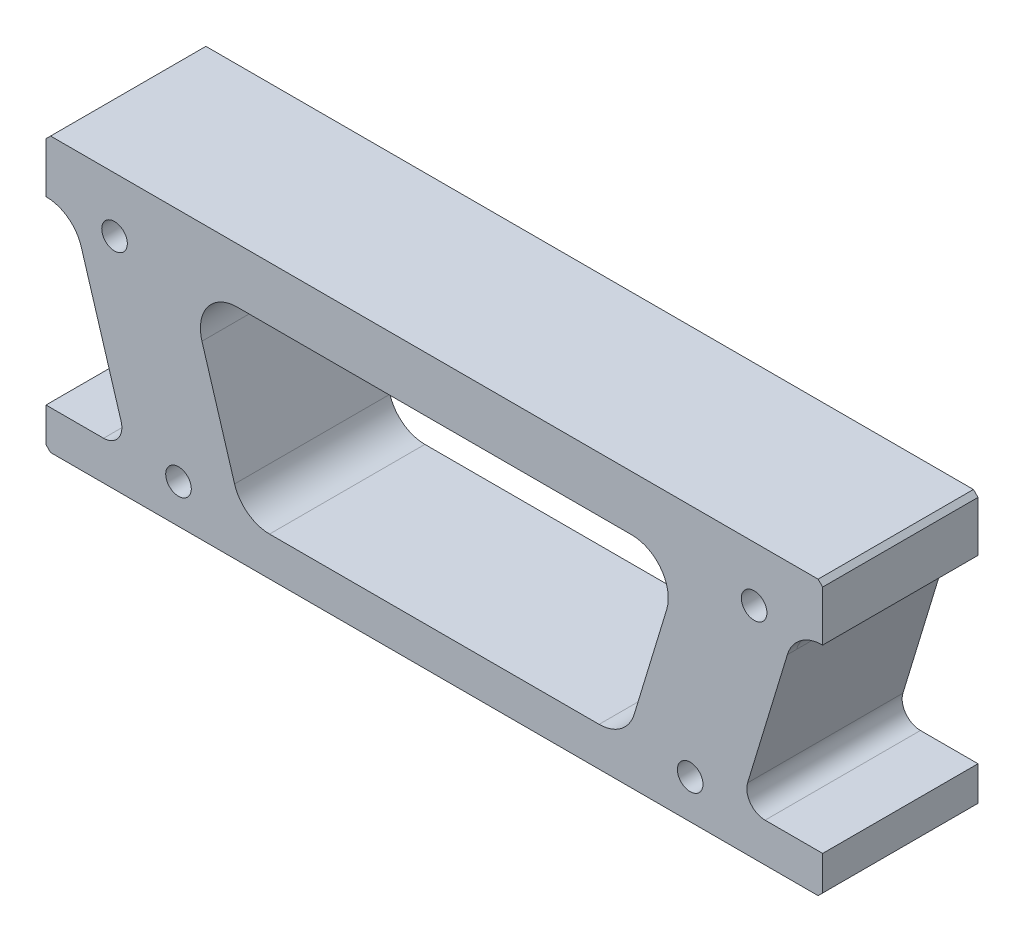
SolidWorks part; units mm, degrees
ref_plane "前视基准面" through (0, 0, 0) normal (0, 0, 1) x (1, 0, 0)
ref_plane "上视基准面" through (0, 0, 0) normal (0, 1, 0) x (1, 0, 0)
ref_plane "右视基准面" through (0, 0, 0) normal (1, 0, 0) x (0, 0, -1)
sketch "草图1" plane through (0, 0, 0) normal (0, 1, 0) x (1, 0, 0)
  line L1 (-42.5, 7.5) -> (42.5, 7.5)
  line L2 (-42.5, 7.5) -> (-42.5, -7.5)
  line L3 (-42.5, -7.5) -> (42.5, -7.5)
  line L4 (42.5, 7.5) -> (42.5, -7.5)
  line L5 (-42.5, 7.5) -> (42.5, -7.5) construction
  line L6 (-42.5, -7.5) -> (42.5, 7.5) construction
  dimension "D1" = 85
  dimension "D2" = 15
extrude "凸台-拉伸1" add sketch "草图1" along normal blind 30
sketch "草图2" plane through (0, 0, 7.5) normal (0, 0, 1) x (1, 0, 0)
  line L0 (0, 30) -> (0, 24) construction
  line L1 (0, 24) -> (-35, 24) construction
  line L2 (0, 24) -> (35, 24) construction
  line L3 (0, 24) -> (0, 4) construction
  line L4 (0, 4) -> (28, 4.2557) construction
  line L5 (0, 4) -> (-28, 4.2557) construction
  line L6 (0, 30) -> (0, 37.6117) construction
  line L7 (-42.5, 30) -> (42.5, 30) construction
  circle A0 centre (-35, 24) radius 1.4
  circle A1 centre (35, 24) radius 1.4
  circle A2 centre (28, 4.2557) radius 1.4
  circle A3 centre (-28, 4.2557) radius 1.4
extrude "切除-拉伸1" cut sketch "草图2" against normal blind 40
sketch "草图3" plane through (0, 0, 7.5) normal (0, 0, 1) x (1, 0, 0)
  line L0 (-27, 24) -> (27, 24)
  line L1 (-27, 24) -> (-21, 4.2557)
  line L2 (-21, 4.2557) -> (21, 4.2557)
  line L3 (0, 0) -> (0, 30) construction
  line L4 (-42.5, 30) -> (42.5, 30) construction
  line L5 (27, 24) -> (21, 4.2557)
  point P12 (0, 4.2557)
  point P13 (0, 24)
extrude "切除-拉伸2" cut sketch "草图3" against normal blind 40
fillet "圆角1" radius 4 4 edges at (-27, 24, 0) (27, 24, 0) (21, 4.2557, 0) (-21, 4.2557, 0)
sketch "草图5" plane through (0, 30, 0) normal (0, 1, 0) x (1, 0, 0)
  line L0 (-20, -4.5) -> (20, -4.5) construction
  line L1 (0, 4.5) -> (0, -4.5) construction
  line L2 (-35, 4.5) -> (0, 4.5) construction
  line L3 (0, 4.5) -> (35, 4.5) construction
  line L4 (0, 7.5) -> (0, 4.5) construction
  circle A0 centre (-35, 4.5) radius 1.8
  circle A1 centre (35, 4.5) radius 1.8
  circle A2 centre (-20, -4.5) radius 1.8
  circle A3 centre (20, -4.5) radius 1.8
  point P0 (0, 0)
extrude "切除-拉伸3" cut sketch "草图5" against normal blind 5
ref_plane "基准面1" through (0, 15, 0) normal (0, 1, 0) x (1, 0, 0)
chamfer "倒角1" distance 0.5 angle 45 4 edges at (-42.5, 0, 0) (42.5, 0, 0) (42.5, 30, 0) (-42.5, 30, 0)
sketch "草图6" plane through (0, 0, 7.5) normal (0, 0, 1) x (1, 0, 0)
  line L0 (-42.5, 24) -> (-39.5, 24)
  line L1 (-42.5, 29.5) -> (-42.5, 0.5) construction
  line L2 (-39.5, 24) -> (-33.5, 4.2557)
  line L3 (-33.5, 4.2557) -> (-42.5, 4.2557)
  line L4 (-25.431, 18.837) -> (-21.8621, 7.0927) construction
  line L5 (-25.431, 18.837) -> (-21.8621, 7.0927) construction
  line L6 (0, 30) -> (0, 0) construction
  line L7 (-42, 30) -> (42, 30) construction
  line L8 (-42.5, 24) -> (-42.5, 4.2557)
  line L9 (42.5, 24) -> (42.5, 4.2557)
  line L10 (33.5, 4.2557) -> (42.5, 4.2557)
  line L11 (39.5, 24) -> (33.5, 4.2557)
  line L12 (42.5, 24) -> (39.5, 24)
extrude "切除-拉伸4" cut sketch "草图6" against normal blind 24
fillet "圆角3" radius 4 2 edges at (39.5, 24, 0) (-39.5, 24, 0)
sketch "草图9" plane through (0, 0, 0) normal (0, -1, 0) x (1, 0, 0)
  circle A0 centre (20, 4.5) radius 1.8 construction
  circle A1 centre (-20, 4.5) radius 1.8 construction
  circle A2 centre (-35, -4.5) radius 1.8 construction
  circle A3 centre (35, -4.5) radius 1.8 construction
  circle A4 centre (20, 4.5) radius 1.8
  circle A5 centre (-20, 4.5) radius 1.8
  circle A6 centre (-35, -4.5) radius 1.8
  circle A7 centre (35, -4.5) radius 1.8
extrude "切除-拉伸5" cut sketch "草图9" against normal blind 5
fillet "圆角4" radius 2 2 edges at (-33.5, 4.2557, 1.9975) (33.5, 4.2557, 1.9975)
sketch "草图10" plane through (0, 0, -7.5) normal (0, 0, -1) x (-1, 0, 0)
  line L0 (42, 30) -> (-42, 30)
  line L1 (-42, 30) -> (-42.5, 29.5)
  line L2 (-42.5, 29.5) -> (-42.5, 24)
  line L3 (-38.6379, 21.163) -> (-34.2845, 6.8372)
  line L4 (-36.1981, 4.2557) -> (-42.5, 4.2557)
  line L5 (-42.5, 4.2557) -> (-42.5, 0.5)
  line L6 (-42.5, 0.5) -> (-42, 0)
  line L7 (-42, 0) -> (42, 0)
  line L8 (42, 0) -> (42.5, 0.5)
  line L9 (42.5, 0.5) -> (42.5, 4.2557)
  line L10 (42.5, 4.2557) -> (36.1981, 4.2557)
  line L11 (34.2845, 6.8372) -> (38.6379, 21.163)
  line L12 (42.5, 24) -> (42.5, 29.5)
  line L13 (42.5, 29.5) -> (42, 30)
  line L14 (21.6038, 24) -> (-21.6038, 24)
  line L15 (18.0349, 4.2557) -> (-18.0349, 4.2557)
  line L16 (25.431, 18.837) -> (21.8621, 7.0927)
  line L17 (-25.431, 18.837) -> (-21.8621, 7.0927)
  line L18 (-34.2845, 6.8372) -> (-40.1361, 26.0931)
  line L19 (-42.5, 24) -> (-39.5, 24)
  line L20 (34.2845, 6.8372) -> (39.7719, 24.8948)
  line L21 (42.5, 24) -> (39.5, 24)
  arc A1 (34.2845, 6.8372) -> (36.1981, 4.2557) centre (36.1981, 6.2557) ccw
  arc A3 (-34.2845, 6.8372) -> (-36.1981, 4.2557) centre (-36.1981, 6.2557) cw
  arc A4 (21.6038, 24) -> (25.431, 18.837) centre (21.6038, 20) cw
  arc A5 (21.8621, 7.0927) -> (18.0349, 4.2557) centre (18.0349, 8.2557) cw
  arc A6 (-21.6038, 24) -> (-25.431, 18.837) centre (-21.6038, 20) ccw
  arc A7 (-21.8621, 7.0927) -> (-18.0349, 4.2557) centre (-18.0349, 8.2557) ccw
  circle A8 centre (35, 24) radius 1.4
  circle A9 centre (28, 4.2557) radius 1.4
  circle A10 centre (-28, 4.2557) radius 1.4
  circle A11 centre (-35, 24) radius 1.4
  dimension "D1" = 2.8
extrude "凸台-拉伸3" add sketch "草图10" along normal blind 1 and the other way blind 16
fillet "圆角5" radius 4 4 edges at (39.5, 24, -8) (39.5, 24, 8) (-39.5, 24, -8) (-39.5, 24, 8)
